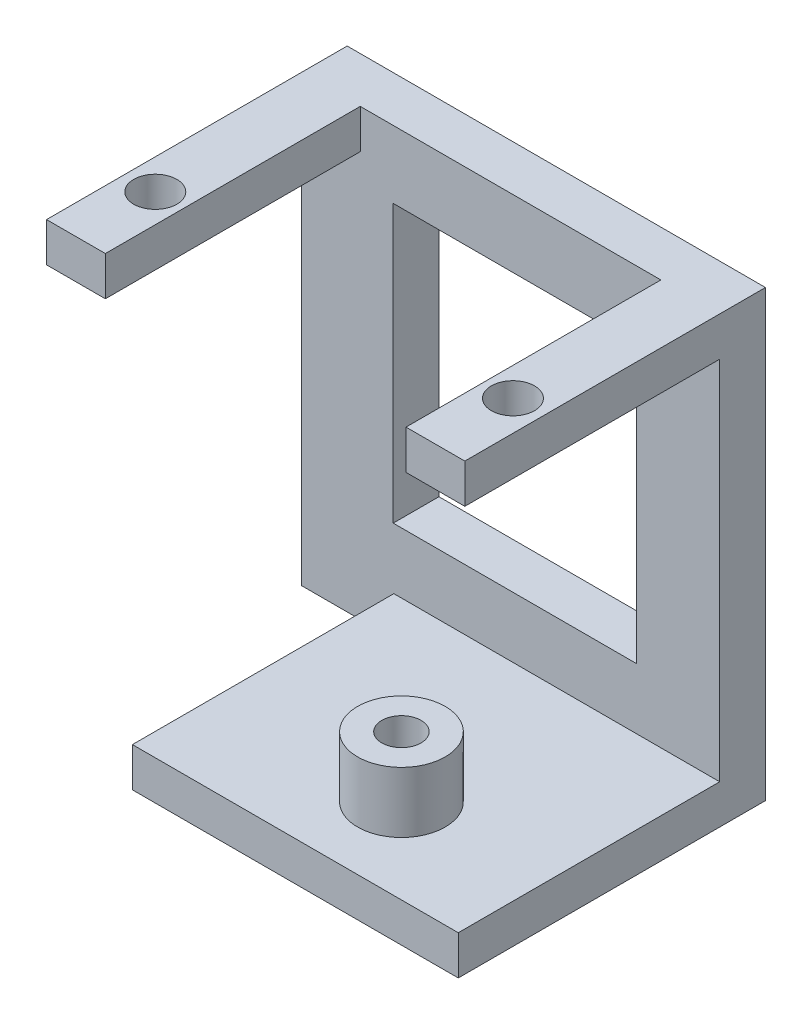
SolidWorks part; units mm, degrees
ref_plane "前视基准面" through (0, 0, 0) normal (0, 0, 1) x (1, 0, 0)
ref_plane "上视基准面" through (0, 0, 0) normal (0, 1, 0) x (1, 0, 0)
ref_plane "右视基准面" through (0, 0, 0) normal (1, 0, 0) x (0, 0, -1)
sketch "草图1" plane through (0, 0, 0) normal (0, 1, 0) x (1, 0, 0)
  line L0 (0, 5.3451) -> (0, 14.3596) construction
  line L13 (-16, 17) -> (-11.5, 17)
  line L14 (-16, 17) -> (-16, -6)
  line L19 (-16, -6) -> (-11.5, -6)
  line L20 (-11.5, 17) -> (-11.5, -6)
  line L21 (-16, 17) -> (-11.5, -6) construction
  line L22 (-16, -6) -> (-11.5, 17) construction
  line L23 (11.5, 17) -> (16, 17)
  line L24 (11.5, 17) -> (11.5, -6)
  line L25 (11.5, -6) -> (16, -6)
  line L26 (16, 17) -> (16, -6)
  line L27 (11.5, 17) -> (16, -6) construction
  line L28 (11.5, -6) -> (16, 17) construction
  line L29 (-11.5, 12.2078) -> (11.5, 12.2078) construction
  line L30 (0, -55) -> (0, 55) construction
  point P4 (-13.75, 5.5)
  point P9 (13.75, 5.5)
  point P14 (0, 12.2078)
  point P15 (0, 0)
  point P16 (0, 0)
  dimension "D1" = 23
  dimension "D2" = 6
  dimension "D3" = 23
  dimension "D4" = 4.5
extrude "凸台-拉伸1" add sketch "草图1" along normal mid plane 3
sketch "草图2" plane through (0, 0, 0) normal (0, 1, 0) x (1, 0, 0)
  line L0 (-13.68, 0) -> (13.68, 0) construction
  circle A0 centre (-13.68, 0) radius 1.65
  circle A1 centre (13.68, 0) radius 1.65
  point P3 (0, 0)
  point P6 (0, 0)
  dimension "D2" = 3.3
  dimension "D3" = 3.3
  dimension "D1" = 27.36
extrude "切除-拉伸1" cut sketch "草图2" against normal through all both and the other way through all
sketch "草图4" plane through (-11.5, 0, 0) normal (1, 0, 0) x (0, 0, -1)
  line L0 (-6, -1.5) -> (17, -1.5) construction
  line L1 (17, 1.5) -> (13.5, 1.5)
  line L2 (17, 1.5) -> (17, -1.5)
  line L3 (17, -1.5) -> (13.5, -1.5)
  line L4 (13.5, 1.5) -> (13.5, -1.5)
  line L5 (17, 1.5) -> (13.5, -1.5) construction
  line L6 (17, -1.5) -> (13.5, 1.5) construction
  point P4 (15.25, 0)
  dimension "D1" = 3.5
extrude "凸台-拉伸3" add sketch "草图4" along normal up to next (23 mm away)
sketch "草图3" plane through (-11.5, 0, 0) normal (1, 0, 0) x (0, 0, -1)
  line L0 (-6, 1.5) -> (17, 1.5) construction
  line L1 (6.5, 1.5) -> (8.5, 1.5)
  line L2 (6.5, 1.5) -> (6.5, -1.5)
  line L3 (6.5, -1.5) -> (8.5, -1.5)
  line L4 (8.5, 1.5) -> (8.5, -1.5)
  line L5 (6.5, 1.5) -> (8.5, -1.5) construction
  line L6 (6.5, -1.5) -> (8.5, 1.5) construction
  line L7 (-6, -1.5) -> (17, -1.5) construction
  line L8 (-6, 1.5) -> (-6, -1.5) construction
  point P4 (7.5, 0)
  dimension "D1" = 12.5
  dimension "D2" = 2
sketch "草图5" plane through (0, -1.5, 0) normal (0, -1, 0) x (-1, 0, 0)
  line L1 (-16, 13.5) -> (16, 13.5)
  line L2 (-16, 13.5) -> (-16, 17)
  line L3 (-16, 17) -> (16, 17)
  line L4 (16, 13.5) -> (16, 17)
  line L5 (-16, 13.5) -> (16, 17) construction
  line L6 (-16, 17) -> (16, 13.5) construction
  line L7 (-11.5, 13.5) -> (11.5, 13.5) construction
  line L42 (-16, 17) -> (-16, -6) construction
  point P4 (0, 15.25)
  point P10 (-11.3795, 15.5)
  point P11 (-11.3795, 19)
  point P12 (-11.3795, 19)
  point P13 (-11.3795, 15.5)
  point P14 (-11.3795, 19)
  point P15 (11.6205, 19)
  point P16 (-11.3795, 15.5)
  point P17 (11.6205, 15.5)
  point P18 (-11.3795, 15.5)
  point P19 (11.6205, 15.5)
  point P20 (-11.3795, 19)
  point P21 (11.6205, 19)
  point P22 (11.6205, 19)
  point P23 (11.6205, 15.5)
  point P24 (11.6205, 15.5)
  point P25 (11.6205, 19)
  point P26 (11.6205, 19)
  point P27 (16.4112, 19)
  point P28 (11.6205, -6)
  point P29 (11.6205, 19)
  point P30 (16.4112, -6)
  point P31 (11.6205, -6)
  point P32 (16.4112, 19)
  point P33 (16.4112, -6)
  point P34 (11.6205, 19)
  point P35 (16.4112, 19)
  point P36 (11.6205, -6)
  point P37 (11.6205, 19)
  point P38 (16.4112, -6)
  point P39 (11.6205, -6)
  point P40 (16.4112, 19)
  point P41 (16.4112, -6)
  point P42 (13.68, 0)
  point P43 (15.2579, 0.4824)
  point P44 (13.68, 0)
  point P45 (15.2579, 0.4824)
  point P46 (-11.3795, 19)
  point P47 (-11.3795, -6)
  point P48 (-11.3795, -6)
  point P49 (-16.1703, -6)
  point P50 (-16.1703, -6)
  point P51 (-16.1703, 19)
  point P52 (-16.1703, 19)
  point P53 (-11.3795, 19)
  point P54 (-11.3795, 19)
  point P55 (-11.3795, -6)
  point P56 (-11.3795, -6)
  point P57 (-16.1703, -6)
  point P58 (-16.1703, -6)
  point P59 (-16.1703, 19)
  point P60 (-16.1703, 19)
  point P61 (-11.3795, 19)
  point P62 (-13.68, 0)
  point P63 (-12.1021, 0.4824)
  point P64 (-13.68, 0)
  point P65 (-12.1021, 0.4824)
  point P66 (0.1205, -199992.6549)
  point P67 (0.1205, 200016.3596)
  point P68 (16.4112, 19)
  point P69 (11.6205, 19)
  point P70 (16.4112, 19)
  point P71 (16.4112, -6)
  point P72 (16.4112, -6)
  point P73 (11.6205, -6)
  point P74 (11.6205, 19)
  point P75 (11.6205, -6)
  point P76 (16.4112, 19)
  point P77 (11.6205, -6)
  point P78 (16.4112, -6)
  point P79 (11.6205, 19)
  point P80 (-11.3795, 19)
  point P81 (-16.1703, 19)
  point P82 (-11.3795, 19)
  point P83 (-11.3795, -6)
  point P84 (-11.3795, -6)
  point P85 (-16.1703, -6)
extrude "凸台-拉伸4" add sketch "草图5" along normal blind 31
sketch "草图6" plane through (0, 0, -13.5) normal (0, 0, 1) x (1, 0, 0)
  line L0 (-16, -32.5) -> (-16, -1.5) construction
  line L1 (-16, -29.5) -> (16, -29.5)
  line L2 (-16, -29.5) -> (-16, -32.5)
  line L3 (-16, -32.5) -> (16, -32.5)
  line L4 (16, -29.5) -> (16, -32.5)
  line L5 (-16, -29.5) -> (16, -32.5) construction
  line L6 (-16, -32.5) -> (16, -29.5) construction
  point P4 (0, -31)
  dimension "D1" = 3
extrude "凸台-拉伸5" add sketch "草图6" along normal blind 20
sketch "草图7" plane through (0, -29.5, 0) normal (0, 1, 0) x (1, 0, 0)
  line L0 (-13.68, 0) -> (13.68, 0) construction
  point P0 (0, 0)
  point P1 (5.15, 0)
  point P6 (0, 0)
  dimension "D1" = 27.36
  dimension "D2" = 8.53
sketch "草图8" plane through (0, -29.5, 0) normal (0, 1, 0) x (1, 0, 0)
  circle A0 centre (5.15, 0) radius 3.35
  dimension "D1" = 6.7
extrude "凸台-拉伸6" add sketch "草图8" along normal blind 6
sketch "草图9" plane through (0, -23.5, 0) normal (0, 1, 0) x (1, 0, 0)
  circle A0 centre (5.15, 0) radius 1.5
  dimension "D1" = 3
extrude "切除-拉伸2" cut sketch "草图9" against normal up to next
sketch "草图10" plane through (0, 0, -17) normal (0, 0, -1) x (-1, 0, 0)
  line L1 (-9.6277, -3.6672) -> (8.9791, -3.6672)
  line L2 (-9.6277, -3.6672) -> (-9.6277, -24.8524)
  line L3 (-9.6277, -24.8524) -> (8.9791, -24.8524)
  line L4 (8.9791, -3.6672) -> (8.9791, -24.8524)
  line L5 (-9.6277, -3.6672) -> (8.9791, -24.8524) construction
  line L6 (-9.6277, -24.8524) -> (8.9791, -3.6672) construction
  point P4 (-0.3243, -14.2598)
extrude "切除-拉伸3" cut sketch "草图10" against normal through all
sketch "草图11" plane through (0, -29.5, 0) normal (0, 1, 0) x (1, 0, 0)
  line L0 (16, -6.5) -> (-16, -6.5) construction
  line L5 (-16, 13.5) -> (-8.9302, 13.5)
  line L6 (-16, 13.5) -> (-16, -6.5)
  line L7 (-16, -6.5) -> (-8.9302, -6.5)
  line L8 (-8.9302, 13.5) -> (-8.9302, -6.5)
  line L9 (-16, 13.5) -> (-8.9302, -6.5) construction
  line L10 (-16, -6.5) -> (-8.9302, 13.5) construction
  point P4 (-12.4651, 3.5)
extrude "切除-拉伸4" cut sketch "草图11" against normal blind 10
